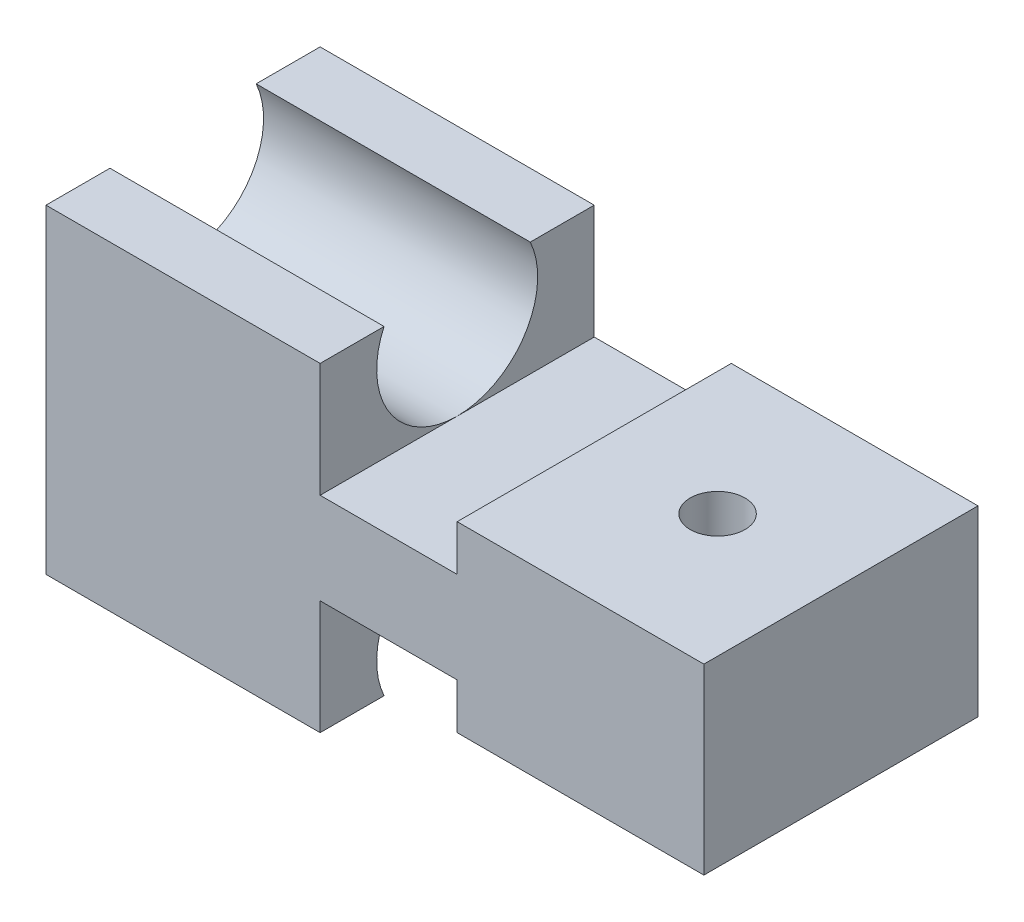
SolidWorks part; units mm, degrees
note: The reader was unsure of these and kept them because the rebuilt part matched: shared geometry of "Sketch1<3>".
ref_plane "Front Plane" through (0, 0, 0) normal (0, 0, 1) x (1, 0, 0)
ref_plane "Top Plane" through (0, 0, 0) normal (0, 1, 0) x (1, 0, 0)
ref_plane "Right Plane" through (0, 0, 0) normal (1, 0, 0) x (0, 0, -1)
sketch "Sketch1" plane through (0, 0, 0) normal (0, 0, 1) x (1, 0, 0)
  line L0 (0, 0) -> (43.1445, 0) construction
  line L1 (-15, -17.5) -> (15, -17.5)
  line L2 (-15, -17.5) -> (-15, 17.5)
  line L3 (-15, 17.5) -> (15, 17.5)
  line L4 (15, -17.5) -> (15, 17.5)
  line L5 (-15, -17.5) -> (15, 17.5) construction
  line L6 (-15, 17.5) -> (15, -17.5) construction
  line L12 (30, -10) -> (57, -10)
  line L13 (30, -10) -> (30, 10)
  line L14 (30, 10) -> (57, 10)
  line L15 (57, -10) -> (57, 10)
  line L16 (30, -10) -> (57, 10) construction
  line L17 (30, 10) -> (57, -10) construction
  line L19 (15, -5) -> (30, -5)
  line L20 (15, -5) -> (15, 5)
  line L21 (15, 5) -> (30, 5)
  line L22 (30, -5) -> (30, 5)
  circle A0 centre (15, 0) radius 1.5
  point P1 (0, 0)
  point P10 (43.5, 0)
  point P14 (22.5, 0)
  dimension "D7" = 3
  dimension "D1" = 35
  dimension "D2" = 5
  dimension "D3" = 30
  dimension "D4" = 30
  dimension "D5" = 27
  dimension "D6" = 20
  dimension "D9" = 10
extrude "Boss-Extrude1" add sketch "Sketch1" along normal blind 30
sketch "Sketch5" plane through (-15, 0, 0) normal (-1, 0, 0) x (0, 0, 1)
  line L0 (0, -20.5) -> (30.4393, -20.5) construction
  line L1 (30, -17.5) -> (0, -17.5) construction
  line L3 (0, 0) -> (30, 0) construction
  line L4 (30, -17.5) -> (30, 17.5) construction
  line L5 (7, -17.5) -> (23, -17.5)
  line L7 (7, 17.5) -> (23, 17.5)
  arc A0 (7, -17.5) -> (23, -17.5) centre (15, -13.81) cw
  arc A1 (7, 17.5) -> (23, 17.5) centre (15, 13.81) ccw
  point P25 (15, 5)
  point P26 (15, -5)
  dimension "D3" = 10
  dimension "D4" = 7
  dimension "D1" = 3
  dimension "D2" = 7
extrude "Cut-Extrude1" cut sketch "Sketch1<3>" along normal blind 8 contours L20 A0 | L20 A0
sketch "Sketch1<3>" plane through (0, 0, 0) normal (0, 0, 1) x (1, 0, 0) same geometry as "Sketch1"
sketch "Sketch15" plane through (0, 10, 0) normal (0, 1, 0) x (1, 0, 0)
  line L0 (30, 0) -> (57, 0) construction
  line L1 (57, -30) -> (57, 0) construction
  circle A0 centre (43.5, -6) radius 1.5
  circle A1 centre (43.5, -15) radius 3
  dimension "D1" = 3
  dimension "D4" = 9
  dimension "D5" = 6
  dimension "D2" = 6
  dimension "D3" = 13.5
  dimension "D6" = 13.5
extrude "Cut-Extrude3" cut sketch "Sketch15" against normal through all contours A1
sketch "Sketch17" plane through (0, -10, 0) normal (0, -1, 0) x (1, 0, 0)
  line L0 (30, 0) -> (57, 0) construction
  line L2 (57, 30) -> (57, 0) construction
  circle A0 centre (43.5, 6) radius 1.5
  circle A1 centre (43.5, 15) radius 3
  dimension "D1" = 9
  dimension "D2" = 3
  dimension "D3" = 6
  dimension "D4" = 6
  dimension "D5" = 13.5
  dimension "D6" = 13.5
extrude "Cut-Extrude6" cut sketch "Sketch5" against normal blind 30
